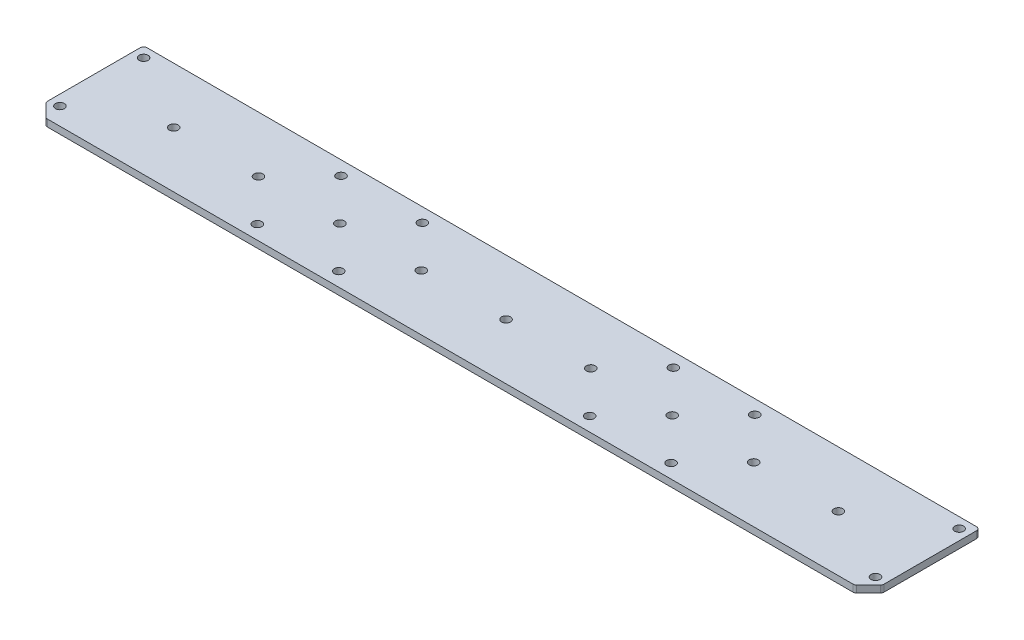
SolidWorks part; units mm, degrees
ref_plane "Front Plane" through (0, 0, 0) normal (0, 0, 1) x (1, 0, 0)
ref_plane "Top Plane" through (0, 0, 0) normal (0, 1, 0) x (1, 0, 0)
ref_plane "Right Plane" through (0, 0, 0) normal (1, 0, 0) x (0, 0, -1)
sketch "Sketch2" plane through (0, 0, 0) normal (0, 1, 0) x (1, 0, 0)
  line L0 (0, 7.0076) -> (0, 50.8)
  line L1 (0, 50.8) -> (381, 50.8)
  line L2 (381, 50.8) -> (381, 7.0076)
  line L3 (373.9924, 0) -> (7.0076, 0)
  line L4 (5.885, 0.465) -> (0.465, 5.885) construction
  line L5 (5.885, 0.465) -> (0.465, 5.885)
  line L6 (375.115, 0.465) -> (380.535, 5.885) construction
  line L7 (375.115, 0.465) -> (380.535, 5.885)
  line L8 (336.6279, 50.8) -> (379.4125, 50.8) construction
  arc A0 (5.885, 0.465) -> (7.0076, 0) centre (7.0076, 1.5875) ccw construction
  arc A1 (0, 7.0076) -> (0.465, 5.885) centre (1.5875, 7.0076) ccw construction
  arc A2 (5.885, 0.465) -> (7.0076, 0) centre (7.0076, 1.5875) ccw
  arc A3 (0, 7.0076) -> (0.465, 5.885) centre (1.5875, 7.0076) ccw
  arc A4 (373.9924, 0) -> (375.115, 0.465) centre (373.9924, 1.5875) ccw construction
  arc A6 (373.9924, 0) -> (375.115, 0.465) centre (373.9924, 1.5875) ccw
  arc A8 (380.535, 5.885) -> (381, 7.0076) centre (379.4125, 7.0076) ccw construction
  arc A9 (380.535, 5.885) -> (381, 7.0076) centre (379.4125, 7.0076) ccw
extrude "Boss-Extrude1" add sketch "Sketch2" along normal blind 3.175
sketch "Sketch3" plane through (0, 0, 0) normal (0, 1, 0) x (1, 0, 0)
  circle A25 centre (4.7625, 7.9375) radius 2.032 construction
  circle A31 centre (4.7625, 46.0375) radius 2.032 construction
  circle A63 centre (376.2375, 7.9375) radius 2.032 construction
  circle A64 centre (376.2375, 46.0375) radius 2.032 construction
  circle A67 centre (4.7625, 7.9375) radius 2.032
  circle A68 centre (4.7625, 46.0375) radius 2.032
  circle A72 centre (376.2375, 7.9375) radius 2.032
  circle A73 centre (376.2375, 46.0375) radius 2.032
  circle A123 centre (341.884, 25.4) radius 2.032 construction
  circle A124 centre (247.65, 44.45) radius 2.032 construction
  circle A125 centre (284.734, 44.45) radius 2.032 construction
  circle A128 centre (247.65, 6.35) radius 2.032 construction
  circle A129 centre (284.734, 6.35) radius 2.032 construction
  circle A132 centre (190.5, 25.4) radius 2.032 construction
  circle A134 centre (170.434, 6.35) radius 2.032 construction
  circle A135 centre (133.35, 44.45) radius 2.032 construction
  circle A136 centre (96.266, 44.45) radius 2.032 construction
  circle A137 centre (96.266, 6.35) radius 2.032 construction
  circle A140 centre (77.724, 25.4) radius 2.032 construction
  circle A141 centre (39.116, 25.4) radius 2.032 construction
  circle A142 centre (341.884, 25.4) radius 2.032
  circle A143 centre (247.65, 44.45) radius 2.032
  circle A144 centre (284.734, 44.45) radius 2.032
  circle A147 centre (247.65, 6.35) radius 2.032
  circle A148 centre (284.734, 6.35) radius 2.032
  circle A151 centre (190.5, 25.4) radius 2.032
  circle A154 centre (133.35, 44.45) radius 2.032
  circle A155 centre (96.266, 44.45) radius 2.032
  circle A156 centre (96.266, 6.35) radius 2.032
  circle A159 centre (77.724, 25.4) radius 2.032
  circle A160 centre (39.116, 25.4) radius 2.032
  circle A161 centre (151.892, 25.4) radius 2.032
  circle A162 centre (229.108, 25.4) radius 2.032
  circle A163 centre (266.192, 25.4) radius 2.032
  circle A164 centre (303.276, 25.4) radius 2.032
  circle A165 centre (151.892, 25.4) radius 2.3813 construction
  circle A166 centre (229.108, 25.4) radius 2.3813 construction
  circle A167 centre (266.192, 25.4) radius 2.3813 construction
  circle A168 centre (303.276, 25.4) radius 2.3813 construction
  circle A169 centre (133.35, 6.35) radius 2.032
  circle A170 centre (114.808, 25.4) radius 2.032 construction
  circle A171 centre (114.808, 25.4) radius 2.032
extrude "Cut-Extrude1" cut sketch "Sketch3" along normal through all
fillet "Fillet1" radius 1.5875 2 edges at (0, 1.5875, -50.8) (381, 1.5875, -50.8)
